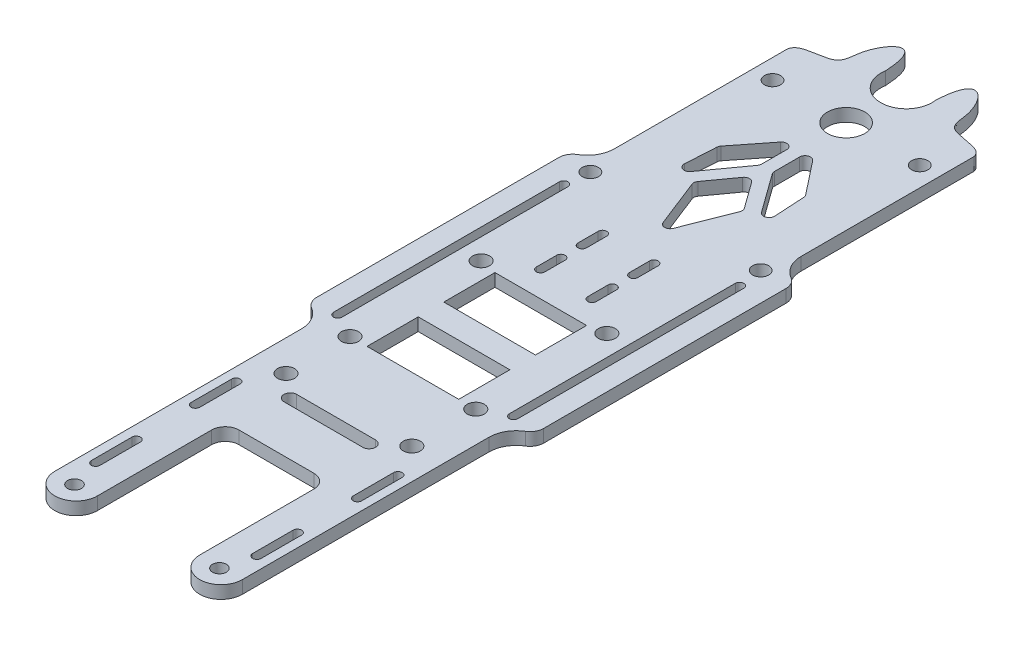
SolidWorks part; units mm, degrees
ref_plane "Front Plane" through (0, 0, 0) normal (0, 0, 1) x (1, 0, 0)
ref_plane "Top Plane" through (0, 0, 0) normal (0, 1, 0) x (1, 0, 0)
ref_plane "Right Plane" through (0, 0, 0) normal (1, 0, 0) x (0, 0, -1)
sketch "Sketch1" plane through (0, 0, 0) normal (0, 1, 0) x (1, 0, 0)
  line L1 (9.5179, -5.1674) -> (51.7851, -5.1674)
  line L2 (9.5179, -5.1674) -> (9.5179, 43.2514)
  line L3 (9.5179, 43.2514) -> (51.7851, 43.2514)
  line L4 (51.7851, -5.1674) -> (51.7851, 43.2514)
  line L5 (13.2882, 43.2514) -> (48.0148, 43.2514)
  line L6 (13.2882, 43.2514) -> (13.2882, 80.3592)
  line L8 (48.0148, 43.2514) -> (48.0148, 80.3592)
  line L9 (22.1187, -6.7549) -> (39.1843, -6.7549)
  line L10 (13.189, -5.1674) -> (48.114, -5.1674)
  line L11 (13.189, -5.1674) -> (13.189, -59.9361)
  line L12 (13.189, -59.9361) -> (21.1265, -59.9361)
  line L13 (48.114, -5.1674) -> (48.114, -59.9361)
  line L14 (22.1187, -6.7549) -> (22.1187, 2.7701)
  line L15 (22.1187, 2.7701) -> (39.1843, 2.7701)
  line L16 (39.1843, -6.7549) -> (39.1843, 2.7701)
  line L20 (35.4351, 21.8201) -> (35.4351, 25.5901) construction
  line L21 (23.3093, -22.233) -> (37.9937, -22.233) construction
  line L22 (34.6413, 21.8201) -> (34.6413, 25.5901)
  line L23 (36.2288, 21.8201) -> (36.2288, 25.5901)
  line L24 (47.0226, -4.3736) -> (47.0226, 37.6951) construction
  line L25 (23.3093, -21.0424) -> (37.9937, -21.0424)
  line L26 (23.3093, -23.4236) -> (37.9937, -23.4236)
  line L27 (22.1187, 7.5326) -> (39.1843, 7.5326)
  line L28 (46.2288, -4.3736) -> (46.2288, 37.6951)
  line L29 (47.8163, -4.3736) -> (47.8163, 37.6951)
  line L30 (22.1187, 7.5326) -> (22.1187, 17.0576)
  line L31 (22.1187, 17.0576) -> (39.1843, 17.0576)
  line L32 (39.1843, 7.5326) -> (39.1843, 17.0576)
  line L33 (45.7327, -32.1549) -> (45.7327, -24.6143) construction
  line L34 (30.6515, 80.3592) -> (30.6515, -32.1549)
  line L35 (44.939, -32.1549) -> (44.939, -24.6143)
  line L36 (46.5265, -32.1549) -> (46.5265, -24.6143)
  line L37 (35.4351, 29.5588) -> (35.4351, 33.3287) construction
  line L38 (34.6413, 29.5588) -> (34.6413, 33.3287)
  line L39 (36.2288, 29.5588) -> (36.2288, 33.3287)
  line L40 (25.8679, 29.5588) -> (25.8679, 33.3287) construction
  line L41 (26.6616, 29.5588) -> (26.6616, 33.3287)
  line L42 (25.0741, 29.5588) -> (25.0741, 33.3287)
  line L43 (25.8679, 21.8201) -> (25.8679, 25.5901) construction
  line L44 (26.6616, 21.8201) -> (26.6616, 25.5901)
  line L45 (25.0741, 21.8201) -> (25.0741, 25.5901)
  line L46 (14.2804, -4.3736) -> (14.2804, 37.6951) construction
  line L47 (15.0741, -4.3736) -> (15.0741, 37.6951)
  line L48 (13.4866, -4.3736) -> (13.4866, 37.6951)
  line L49 (15.5702, -32.1549) -> (15.5702, -24.6143) construction
  line L50 (16.364, -32.1549) -> (16.364, -24.6143)
  line L51 (14.7765, -32.1549) -> (14.7765, -24.6143)
  line L52 (21.1265, -32.1549) -> (40.1765, -32.1549)
  line L53 (40.1765, -32.1549) -> (40.1765, -59.9361)
  line L54 (21.1265, -32.1549) -> (21.1265, -59.9361)
  line L55 (45.6547, -50.808) -> (45.6547, -43.2674) construction
  line L56 (44.861, -50.808) -> (44.861, -43.2674)
  line L57 (46.4485, -50.808) -> (46.4485, -43.2674)
  line L58 (40.1765, -59.9361) -> (48.114, -59.9361)
  line L59 (30.6515, 56.6234) -> (35.2967, 50.1871)
  line L60 (35.2967, 50.1871) -> (30.6515, 38.3671)
  line L61 (31.8421, 66.9801) -> (31.8421, 59.0426)
  line L62 (31.8421, 59.0426) -> (39.2745, 48.7446)
  line L63 (39.2745, 48.7446) -> (38.7221, 58.2536)
  line L64 (38.7221, 58.2536) -> (31.8421, 66.9801)
  line L65 (15.6483, -50.808) -> (15.6483, -43.2674) construction
  line L66 (16.442, -50.808) -> (16.442, -43.2674)
  line L67 (14.8545, -50.808) -> (14.8545, -43.2674)
  line L68 (26.0063, 50.1871) -> (30.6515, 38.3671)
  line L69 (30.6515, 56.6234) -> (26.0063, 50.1871)
  line L70 (22.0285, 48.7446) -> (22.5809, 58.2536)
  line L71 (29.4609, 59.0426) -> (22.0285, 48.7446)
  line L72 (29.4609, 66.9801) -> (29.4609, 59.0426)
  line L73 (22.5809, 58.2536) -> (29.4609, 66.9801)
  circle A0 centre (42.3593, -6.7549) radius 1.5875
  arc A1 (34.6413, 21.8201) -> (36.2288, 21.8201) centre (35.4351, 21.8201) ccw
  arc A2 (36.2288, 25.5901) -> (34.6413, 25.5901) centre (35.4351, 25.5901) ccw
  arc A3 (23.3093, -21.0424) -> (23.3093, -23.4236) centre (23.3093, -22.233) ccw
  arc A4 (37.9937, -23.4236) -> (37.9937, -21.0424) centre (37.9937, -22.233) ccw
  arc A5 (46.2288, -4.3736) -> (47.8163, -4.3736) centre (47.0226, -4.3736) ccw
  arc A6 (47.8163, 37.6951) -> (46.2288, 37.6951) centre (47.0226, 37.6951) ccw
  arc A7 (44.939, -32.1549) -> (46.5265, -32.1549) centre (45.7327, -32.1549) ccw
  arc A8 (46.5265, -24.6143) -> (44.939, -24.6143) centre (45.7327, -24.6143) ccw
  arc A9 (34.6413, 29.5588) -> (36.2288, 29.5588) centre (35.4351, 29.5588) ccw
  arc A10 (36.2288, 33.3287) -> (34.6413, 33.3287) centre (35.4351, 33.3287) ccw
  circle A11 centre (42.3593, 17.6529) radius 1.5875
  circle A12 centre (42.3593, -18.6611) radius 1.5875
  arc A13 (26.6616, 29.5588) -> (25.0741, 29.5588) centre (25.8679, 29.5588) cw
  arc A14 (25.0741, 33.3287) -> (26.6616, 33.3287) centre (25.8679, 33.3287) cw
  arc A15 (26.6616, 21.8201) -> (25.0741, 21.8201) centre (25.8679, 21.8201) cw
  arc A16 (25.0741, 25.5901) -> (26.6616, 25.5901) centre (25.8679, 25.5901) cw
  circle A17 centre (18.9437, 17.6529) radius 1.5875
  arc A18 (15.0741, -4.3736) -> (13.4866, -4.3736) centre (14.2804, -4.3736) cw
  arc A19 (13.4866, 37.6951) -> (15.0741, 37.6951) centre (14.2804, 37.6951) cw
  circle A20 centre (18.9437, -6.7549) radius 1.5875
  circle A21 centre (18.9437, -18.6611) radius 1.5875
  arc A22 (16.364, -32.1549) -> (14.7765, -32.1549) centre (15.5702, -32.1549) cw
  arc A23 (14.7765, -24.6143) -> (16.364, -24.6143) centre (15.5702, -24.6143) cw
  circle A24 centre (46.5048, 42.1456) radius 1.504
  circle A25 centre (30.6515, 73.91) radius 3.4727
  circle A26 centre (44.3594, 73.91) radius 1.504
  arc A27 (44.861, -50.808) -> (46.4485, -50.808) centre (45.6547, -50.808) ccw
  arc A28 (46.4485, -43.2674) -> (44.861, -43.2674) centre (45.6547, -43.2674) ccw
  circle A29 centre (44.1452, -56.265) radius 1.2898
  circle A30 centre (17.1577, -56.265) radius 1.2898
  arc A31 (16.442, -50.808) -> (14.8545, -50.808) centre (15.6483, -50.808) cw
  arc A32 (14.8545, -43.2674) -> (16.442, -43.2674) centre (15.6483, -43.2674) cw
  circle A33 centre (14.7982, 42.1456) radius 1.504
  circle A34 centre (16.9436, 73.91) radius 1.504
  circle A35 centre (30.6515, 85.1217) radius 4.7625
  spline S0 degree 3 poles (35.3427, 85.9429) (35.8139, 94.7404) (40.9626, 89.3168) (40.6952, 81.322) (47.5188, 82.7553) (48.0148, 80.3592) knots 0 0 0 0 0.509252 0.660799 1 1 1 1
  spline S1 degree 3 poles (25.9603, 85.9429) (25.4891, 94.7404) (20.3404, 89.3168) (20.6077, 81.322) (13.7842, 82.7553) (13.2882, 80.3592) knots 0 0 0 0 0.509252 0.660799 1 1 1 1
  point P8 (30.6515, 43.2514)
  point P9 (30.6515, -5.1674)
  point P18 (22.1187, -22.233)
  point P21 (36.2288, 23.7051)
  point P24 (35.4351, 23.7051)
  point P32 (30.6515, -22.233)
  point P39 (30.6515, -6.7549)
  point P40 (47.0226, 16.6607)
  point P46 (45.7327, -28.3846)
  point P53 (35.4351, 21.0264)
  point P64 (35.4351, 31.4438)
  point P72 (35.4351, 28.7651)
  point P73 (35.4351, 26.3838)
  point P77 (45.6547, -47.0377)
  point P83 (39.1843, -22.233)
  point P86 (25.8679, 31.4438)
  point P93 (25.8679, 23.7051)
  point P102 (14.2804, 16.6607)
  point P113 (15.5702, -28.3846)
  point P126 (44.1452, -59.9361)
  point P137 (15.6483, -47.0377)
  point P155 (0, 0)
  dimension "D9" = 3.175
  dimension "D11" = 1.5875
  dimension "D13" = 17.0656
  dimension "D10" = 3.7699
  dimension "D20" = 3.9688
  dimension "D25" = 1.1906
  dimension "D27" = 21.2328
  dimension "D28" = 8.7312
  dimension "D29" = 3.0079
  dimension "D30" = 2.1828
  dimension "D31" = 6.9453
  dimension "D33" = 8.7312
  dimension "D34" = 9.525
  dimension "D35" = 2.5797
  dimension "D49" = 9.525
  dimension "D1" = 48.4187
  dimension "D2" = 42.2672
  dimension "D3" = 37.1078
  dimension "D4" = 34.7266
  dimension "D5" = 54.7687
  dimension "D6" = 34.925
  dimension "D7" = 9.525
  dimension "D8" = 17.0656
  dimension "D12" = 2.3813
  dimension "D14" = 1.5875
  dimension "D15" = 42.0687
  dimension "D16" = 3.9688
  dimension "D17" = 3.175
  dimension "D18" = 14.2875
  dimension "D19" = 4.7625
  dimension "D21" = 10
  dimension "D22" = 1.5875
  dimension "D23" = 1.5875
  dimension "D24" = 19.05
  dimension "D26" = 2.3813
  dimension "D36" = 2.3813
  dimension "D37" = 7.5406
  dimension "D38" = 7.9375
  dimension "D39" = 12.7
  dimension "D40" = 7.9375
  dimension "D41" = 18.2562
  dimension "D42" = 5.5562
  dimension "D43" = 1.1906
  dimension "D44" = 2.3813
  dimension "D45" = 11.1125
  dimension "D46" = 9.525
  dimension "D47" = 12.7
  dimension "D48" = 7.9375
extrude "Boss-Extrude2" add sketch "Sketch1" along normal mid plane 2.3813 contours L1 A20 L10 L11 L12 L34 L26 A3 L25 L9 L14 A21 L51 A23 L50 A22 | A4 L26 L34 L12 L13 L1 L10 A0 L16 L9 L25 A12 A8 L36 A7 L35 | L48 A19 L47 A18 L10 L1 L14 L15 L34 L27 L30 L31 L3 L2 L45 A16 L44 A15 L42 A14 L41 A13 A17 | A6 L29 A5 L1 L4 L3 L5 L34 L31 L32 L27 L15 L16 L10 L28 A11 A10 L39 A9 L38 A2 L23 A1 L22 | L34 L6 L3 | L34 L5 L8 region at (19.2609, 0, -21.2507) region at (20.3568, 0, 27.6946) region at (21.0194, 0, -65.0923) region at (40.9462, 0, 27.6946) region at (40.2836, 0, -65.0932) region at (42.0421, 0, -21.2507)
fillet "Fillet1" radius 5.08 4 edges at (13.2882, 0, -43.2514) (48.0148, 0, -43.2514) (48.114, 0, 5.1674) (13.189, 0, 5.1674)
fillet "Fillet2" radius 2.54 6 edges at (9.5179, 0, 5.1674) (9.5179, 0, -43.2514) (51.7851, 0, -43.2514) (51.7851, 0, 5.1674) (40.1765, 0, 32.1549) (21.1265, 0, 32.1549)
fillet "Fillet5" radius 1.016 12 edges at (29.4609, 0, -59.0426) (22.0285, 0, -48.7446) (22.5809, 0, -58.2536) (29.4609, 0, -66.9801) (30.6515, 0, -38.3671) (35.2967, 0, -50.1871) (26.0063, 0, -50.1871) (30.6515, 0, -56.6234) (39.2745, 0, -48.7446) (38.7221, 0, -58.2536) (31.8421, 0, -59.0426) (31.8421, 0, -66.9801)
fillet "Fillet12" 2 edges at (13.189, 0, 59.9361) (21.1265, 0, 59.9361) type full round first side face at (13.189, 0, 34.9921) second side face at (21.1265, 0, 47.3155) middle face at (17.1577, 0, 59.9361)
fillet "Fillet13" 2 edges at (48.114, 0, 59.9361) (40.1765, 0, 59.9361) type full round first side face at (48.114, 0, 34.9921) second side face at (40.1765, 0, 47.3155) middle face at (44.1452, 0, 59.9361)
